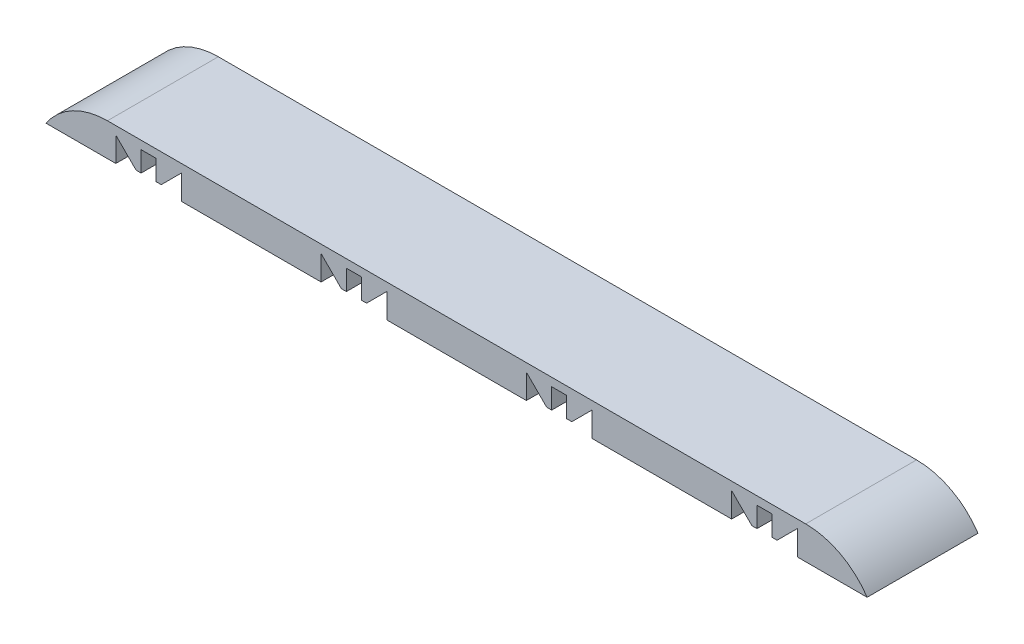
SolidWorks part; units mm, degrees
ref_plane "Front Plane" through (0, 0, 0) normal (0, 0, 1) x (1, 0, 0)
ref_plane "Top Plane" through (0, 0, 0) normal (0, 1, 0) x (1, 0, 0)
ref_plane "Right Plane" through (0, 0, 0) normal (1, 0, 0) x (0, 0, -1)
sketch "Sketch1" plane through (0, 0, 0) normal (0, 1, 0) x (1, 0, 0)
  line L1 (-127, 17.145) -> (127, 17.145)
  line L2 (-127, 17.145) -> (-127, -17.145)
  line L3 (-127, -17.145) -> (127, -17.145)
  line L4 (127, 17.145) -> (127, -17.145)
  line L5 (-127, 17.145) -> (127, -17.145) construction
  line L6 (-127, -17.145) -> (127, 17.145) construction
  point P0 (0, 0)
  dimension "D1" = 34.29
  dimension "D2" = 254
extrude "Boss-Extrude1" add sketch "Sketch1" along normal blind 10.16 contours L2 L1 L4 L3
sketch "Sketch2" plane through (0, 0, 17.145) normal (0, 0, 1) x (1, 0, 0)
  line L2 (-63.5, 0) -> (-63.5, 7.62) construction
  line L3 (-127, 10.16) -> (127, 10.16) construction
  line L4 (-63.5, 10.16) -> (-127, 10.16) construction
  line L5 (-95.25, 36.4746) -> (-95.25, 10.16) construction
  line L6 (-95.25, 10.16) -> (-105.41, 10.16)
  line L8 (-85.09, 7.62) -> (-85.09, 0)
  line L15 (-105.41, 7.62) -> (-105.41, 0)
  line L17 (-97.576, 7.62) -> (-92.924, 7.62)
  line L19 (-95.25, 0) -> (-95.25, -26.692) construction
  line L24 (-105.41, 0) -> (-85.09, 0)
  line L29 (-105.41, 7.62) -> (-99.1452, 1.3552)
  line L30 (-99.1452, 1.3552) -> (-97.576, 1.3552)
  line L31 (-97.576, 1.3552) -> (-97.576, 7.62)
  line L32 (-95.25, 0) -> (-95.25, 7.62) construction
  line L33 (-85.09, 7.62) -> (-91.3548, 1.3552)
  line L34 (-91.3548, 1.3552) -> (-92.924, 1.3552)
  line L35 (-92.924, 1.3552) -> (-92.924, 7.62)
  line L36 (-105.41, 7.62) -> (-105.41, 0)
  line L37 (-85.09, 0) -> (-85.09, 7.62)
  line L38 (-97.576, 7.62) -> (-92.924, 7.62)
  line L60 (-105.41, 0) -> (-85.09, 0)
  line M22 (-127, 0) -> (127, 0)
  dimension "D1" = 20.32
  dimension "D2" = 8.8597
  dimension "D3" = 4.6521
  dimension "D4" = 105.41
  dimension "D5" = 1.5692
  dimension "D6" = 1.3552
  dimension "D7" = 2.54
  dimension "D8" = 2.54
fillet "Fillet1" radius 22.86 2 edges at (-127, 10.16, 0) (127, 10.16, 0)
extrude "Cut-Extrude2" cut sketch "Sketch2" against normal blind 50.8 contours L34 L35 L17 L31 L30 L29 L15 L8 L33 M22 region at (-95.25, 2.9667, 17.145)
pattern_linear "LPattern1" count 4 spacing 63.5 along (1, 0, 0) of "Cut-Extrude2"
